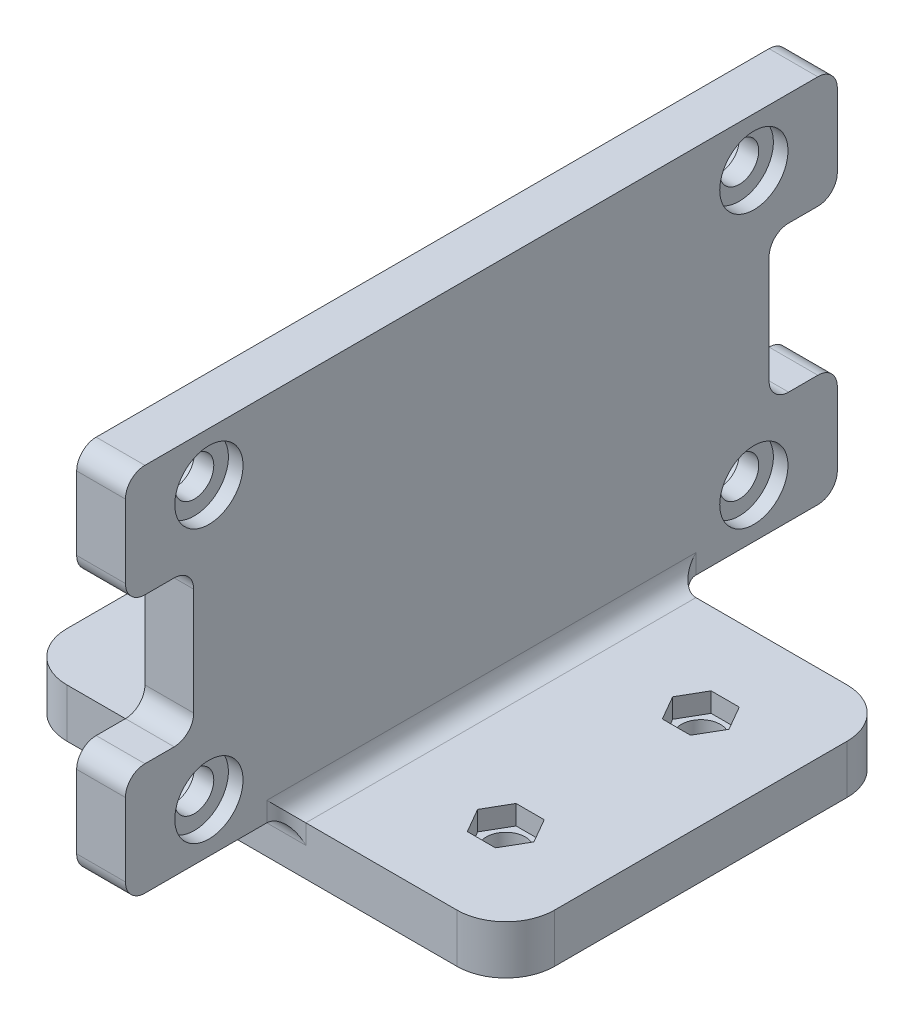
SolidWorks part; units mm, degrees
ref_plane "Plan de face" through (0, 0, 0) normal (0, 0, 1) x (1, 0, 0)
ref_plane "Plan de dessus" through (0, 0, 0) normal (0, 1, 0) x (1, 0, 0)
ref_plane "Plan de droite" through (0, 0, 0) normal (1, 0, 0) x (0, 0, -1)
sketch "Esquisse2" plane through (0, 0, 0) normal (0, 1, 0) x (1, 0, 0)
  line L1 (-25, -20) -> (25, -20)
  line L2 (-25, -20) -> (-25, 20)
  line L3 (-25, 20) -> (25, 20)
  line L4 (25, -20) -> (25, 20)
  line L5 (-25, -20) -> (25, 20) construction
  line L6 (-25, 20) -> (25, -20) construction
  point P0 (0, 0)
  dimension "D1" = 50
  dimension "D2" = 40
extrude "Boss.-Extru.1" add sketch "Esquisse2" along normal blind 5
sketch "Esquisse3" plane through (0, 0, 0) normal (1, 0, 0) x (0, 0, -1)
  line L1 (-36.5, 5) -> (36.5, 5)
  line L2 (-36.5, 5) -> (-36.5, 43)
  line L3 (-36.5, 43) -> (36.5, 43)
  line L4 (36.5, 5) -> (36.5, 43)
  line L5 (0, 5) -> (0, 0) construction
  line L6 (-20, 5) -> (20, 5) construction
  dimension "D1" = 38
  dimension "D2" = 73
extrude "Boss.-Extru.2" add sketch "Esquisse3" along normal mid plane 5
sketch "Esquisse4" plane through (2.5, 0, 0) normal (1, 0, 0) x (0, 0, -1)
  line L0 (-27.94, 37.97) -> (-27.94, 10.03) construction
  line L1 (-27.94, 10.03) -> (27.94, 10.03) construction
  line L2 (27.94, 10.03) -> (27.94, 37.97) construction
  line L3 (27.94, 37.97) -> (-27.94, 37.97) construction
  line L4 (0, 10.03) -> (0, 0) construction
  line L5 (-27.94, 24) -> (-36.5, 24) construction
  line L6 (-36.5, 43) -> (-36.5, 5) construction
  circle A0 centre (-27.94, 37.97) radius 2
  circle A1 centre (-27.94, 10.03) radius 2
  circle A2 centre (27.94, 37.97) radius 2
  circle A3 centre (27.94, 10.03) radius 2
  dimension "D1" = 4
  dimension "D2" = 4
  dimension "D3" = 4
  dimension "D4" = 55.88
  dimension "D5" = 27.94
extrude "Enlèv. mat.-Extru.1" cut sketch "Esquisse4" against normal up to next
sketch "Esquisse5" plane through (2.5, 0, 0) normal (1, 0, 0) x (0, 0, -1)
  line L0 (-36.5, 43) -> (-36.5, 5) construction
  line L1 (-36.5, 31.5) -> (-29.5, 31.5)
  line L2 (-36.5, 31.5) -> (-36.5, 16.5)
  line L3 (-36.5, 16.5) -> (-29.5, 16.5)
  line L4 (-29.5, 31.5) -> (-29.5, 16.5)
  line L5 (-36.5, 24) -> (-29.5, 24) construction
  line L7 (0, 0) -> (0, 16.9686) construction
  line L8 (-20, 0) -> (20, 0) construction
  line L9 (36.5, 16.5) -> (29.5, 16.5)
  line L10 (29.5, 31.5) -> (29.5, 16.5)
  line L11 (36.5, 31.5) -> (29.5, 31.5)
  line L12 (36.5, 31.5) -> (36.5, 16.5)
  dimension "D1" = 7
  dimension "D2" = 15
extrude "Enlèv. mat.-Extru.2" cut sketch "Esquisse5" against normal up to next
fillet "Congé1" radius 2 14 edges at (0, 5, -36.5) (0, 16.5, -29.5) (0, 16.5, -36.5) (0, 31.5, -29.5) (0, 43, -36.5) (0, 31.5, -36.5) (0, 16.5, 29.5) (0, 5, 36.5) (0, 16.5, 36.5) (0, 31.5, 29.5) (0, 31.5, 36.5) (0, 43, 36.5) (-2.5, 5, 0) (2.5, 5, 0)
fillet "Congé2" radius 5 4 edges at (-25, 2.5, 20) (-25, 2.5, -20) (25, 2.5, 20) (25, 2.5, -20)
fillet "Congé3" radius 2 6 edges at (-2.5, 6, 20) (2.5, 6, 20) (0, 5, 20) (2.5, 6, -20) (-2.5, 6, -20) (0, 5, -20)
sketch "Esquisse6" plane through (0, 5, 0) normal (0, 1, 0) x (1, 0, 0)
  line L0 (0, 0) -> (-15, 0) construction
  line L1 (-15, 10) -> (-15, -10) construction
  line L3 (0, 0) -> (0, 8.8966) construction
  line L9 (-12.1132, 10) -> (-13.5566, 12.5)
  line L10 (-13.5566, 12.5) -> (-16.4434, 12.5)
  line L11 (-16.4434, 12.5) -> (-17.8868, 10)
  line L17 (-17.8868, 10) -> (-16.4434, 7.5)
  line L18 (-16.4434, 7.5) -> (-13.5566, 7.5)
  line L19 (-13.5566, 7.5) -> (-12.1132, 10)
  line L26 (-12.1132, -10) -> (-13.5566, -7.5)
  line L27 (-13.5566, -7.5) -> (-16.4434, -7.5)
  line L28 (-16.4434, -7.5) -> (-17.8868, -10)
  line L35 (-17.8868, -10) -> (-16.4434, -12.5)
  line L36 (-16.4434, -12.5) -> (-13.5566, -12.5)
  line L37 (-13.5566, -12.5) -> (-12.1132, -10)
  line L39 (13.5566, -12.5) -> (12.1132, -10)
  line L40 (16.4434, -12.5) -> (13.5566, -12.5)
  line L41 (17.8868, -10) -> (16.4434, -12.5)
  line L42 (16.4434, -7.5) -> (17.8868, -10)
  line L43 (13.5566, -7.5) -> (16.4434, -7.5)
  line L44 (12.1132, -10) -> (13.5566, -7.5)
  line L45 (13.5566, 7.5) -> (12.1132, 10)
  line L46 (16.4434, 7.5) -> (13.5566, 7.5)
  line L47 (17.8868, 10) -> (16.4434, 7.5)
  line L48 (16.4434, 12.5) -> (17.8868, 10)
  line L49 (13.5566, 12.5) -> (16.4434, 12.5)
  line L50 (12.1132, 10) -> (13.5566, 12.5)
  line L51 (-25, 15) -> (-25, -15) construction
  circle A4 centre (-15, 10) radius 2.5 construction
  circle A5 centre (-15, -10) radius 2.5 construction
  point P5 (-15, 0)
  dimension "D2" = 10
  dimension "D1" = 20
  dimension "D3" = 5
extrude "Enlèv. mat.-Extru.3" cut sketch "Esquisse6" against normal blind 2
ref_plane "Plan1" through (-1, 0, 0) normal (1, 0, 0) x (0, 0, -1)
sketch "Esquisse7" plane through (-1, 0, 0) normal (-1, 0, 0) x (0, 0, 1)
  circle A0 centre (-27.94, 37.97) radius 3.5
  circle A1 centre (-27.94, 10.03) radius 3.5
  circle A2 centre (27.94, 37.97) radius 3.5
  circle A3 centre (27.94, 10.03) radius 3.5
  dimension "D1" = 7
extrude "Enlèv. mat.-Extru.4" cut sketch "Esquisse7" along normal up to next
mirror "Symétrie3" about plane through (0, 0, 0) normal (1, 0, 0) of "Enlèv. mat.-Extru.4"
sketch "Esquisse8" plane through (0, 3, 0) normal (0, 1, 0) x (1, 0, 0)
  line L0 (0, 0) -> (0, 8.8966) construction
  line L1 (0, 0) -> (0, 8.8966) construction
  circle A0 centre (-15, 10) radius 2
  circle A1 centre (-15, -10) radius 2
  circle A2 centre (15, -10) radius 2
  circle A3 centre (15, 10) radius 2
  dimension "D1" = 4
extrude "Enlèv. mat.-Extru.5" cut sketch "Esquisse8" against normal up to next
